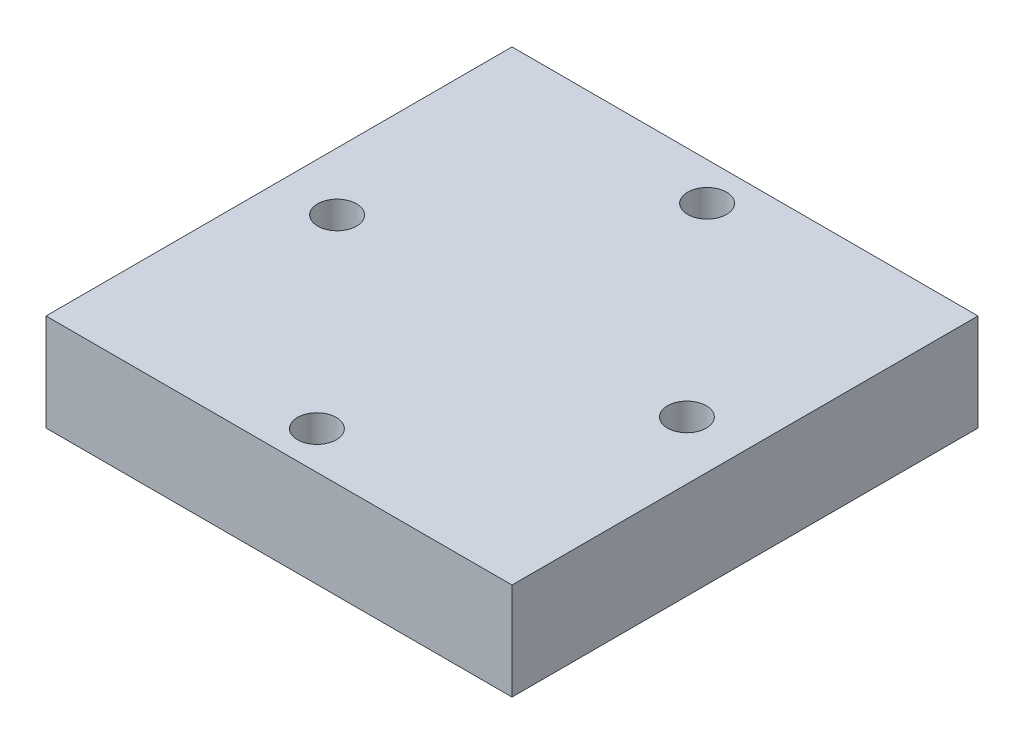
SolidWorks part; units mm, degrees
ref_plane "Front Plane" through (0, 0, 0) normal (0, 0, 1) x (1, 0, 0)
ref_plane "Top Plane" through (0, 0, 0) normal (0, 1, 0) x (1, 0, 0)
ref_plane "Right Plane" through (0, 0, 0) normal (1, 0, 0) x (0, 0, -1)
sketch "Sketch1" plane through (0, 0, 0) normal (0, 1, 0) x (1, 0, 0)
  line L0 (0, 0) -> (76.2, 0)
  line L1 (0, 0) -> (0, 76.2)
  line L2 (0, 76.2) -> (76.2, 76.2)
  line L3 (76.2, 76.2) -> (76.2, 0)
  dimension "D1" = 76.2
  dimension "D2" = 76.2
extrude "Boss-Extrude1" add sketch "Sketch1" along normal blind 15.875
sketch "Sketch2" plane through (0, 15.875, 0) normal (0, 1, 0) x (1, 0, 0)
  line L0 (38.1, 76.2) -> (38.1, 70.0023)
  line L1 (76.2, 76.2) -> (0, 76.2) construction
  line L2 (0, 38.1) -> (76.2, 38.1) construction
  line L3 (0, 76.2) -> (0, 0) construction
  line L4 (76.2, 0) -> (76.2, 76.2) construction
  line L5 (38.1, 0) -> (38.1, 6.1977)
  line L6 (38.1, 66.8273) -> (38.1, 9.3727) construction
  line L7 (0, 38.1) -> (9.4996, 38.1)
  line L8 (76.2, 38.1) -> (66.7004, 38.1)
  circle A0 centre (38.1, 70.0023) radius 3.175
  circle A1 centre (38.1, 6.1977) radius 3.175
  circle A2 centre (9.4996, 38.1) radius 3.175
  circle A3 centre (66.7004, 38.1) radius 3.175
  dimension "D2" = 6.35
  dimension "D4" = 6.35
  dimension "D1" = 6.1977
  dimension "D3" = 9.4996
extrude "Cut-Extrude1" cut sketch "Sketch2" against normal through all contours A0 | A1 region at (35.9184, 15.875, -67.8207) region at (40.2816, 15.875, -4.0161)
extrude "Cut-Extrude2" cut sketch "Sketch2<3>" against normal through all contours A3 | A2 region at (9.4996, 15.875, -35.0148) region at (63.6152, 15.875, -38.1)
sketch "Sketch2<3>" plane through (0, 15.875, 0) normal (0, 1, 0) x (1, 0, 0) same geometry as "Sketch2"
